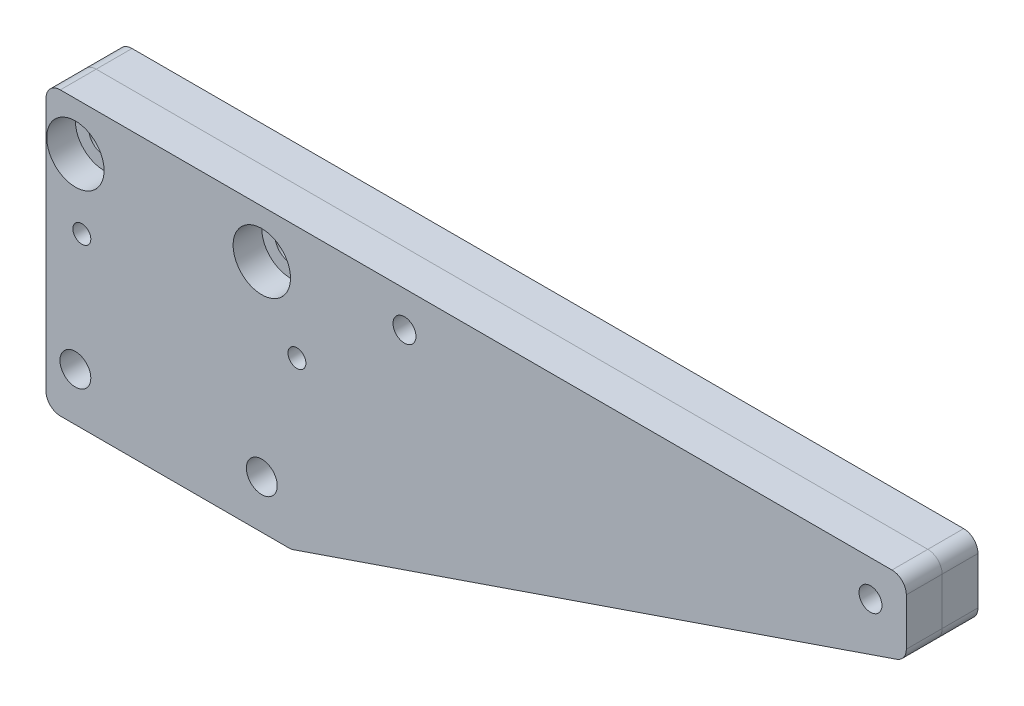
SolidWorks part; units mm, degrees
material "AISI 1045 Steel, cold drawn"
ref_plane "Front Plane" through (0, 0, 0) normal (0, 0, 1) x (1, 0, 0)
ref_plane "Top Plane" through (0, 0, 0) normal (0, 1, 0) x (1, 0, 0)
ref_plane "Right Plane" through (0, 0, 0) normal (1, 0, 0) x (0, 0, -1)
sketch "Sketch1" plane through (0, 0, 0) normal (0, 0, 1) x (1, 0, 0)
  line L0 (17.1, 19.7) -> (102.9, 19.7)
  line L1 (13, -13) -> (-13, -13) construction
  line L2 (13, -13) -> (13, 13) construction
  line L3 (13, 13) -> (-13, 13) construction
  line L4 (-13, -13) -> (-13, 13) construction
  line L5 (13, -13) -> (-13, 13) construction
  line L6 (13, 13) -> (-13, -13) construction
  line L7 (17.1, -19.7) -> (-17.1, -19.7)
  line L8 (17.1, -19.7) -> (17.1, 19.7) construction
  line L9 (17.1, 19.7) -> (-17.1, 19.7)
  line L10 (-17.1, -19.7) -> (-17.1, 19.7)
  line L11 (17.1, -19.7) -> (-17.1, 19.7) construction
  line L12 (17.1, 19.7) -> (-17.1, -19.7) construction
  line L13 (102.9, 19.7) -> (102.9, 9.7)
  line L14 (102.9, 9.7) -> (17.1, -19.7)
  point P0 (0, 0)
  point P6 (0, 0)
  dimension "D1" = 39.4
  dimension "D2" = 120
  dimension "D3" = 34.2
  dimension "D4" = 26
  dimension "D5" = 10
extrude "Boss-Extrude1" add sketch "Sketch1" along normal blind 5
hole_wizard "CBORE for M4 SHCS1" positions "Sketch2" profile "Sketch3" counterbore size "M4" standard "ANSI Metric" end condition through all
sketch "Sketch2" plane through (0, 0, 5) normal (0, 0, 1) x (1, 0, 0)
  point P0 (13, 13)
  point P3 (-13, 13)
sketch "Sketch3" plane through (13, 13, 5) normal (1, 0, 0) x (0, -1, 0)
  line L0 (0, 0) -> (0, 5)
  line L1 (0, 5) -> (2.15, 5)
  line L3 (2.15, 5) -> (2.15, 4)
  line L4 (2.15, 4) -> (4, 4)
  line L5 (4, 4) -> (4, 0)
  line L7 (4, 0) -> (0, 0)
  line L11 (0, -6.35) -> (0, 107.95) construction
  dimension "Thru Hole Dia." = 4.3
  dimension "Thru Hole Depth" = 5
  dimension "C'Bore Dia." = 8
  dimension "C'Bore Depth" = 4
hole_wizard "M4 Clearance Hole1" positions "Sketch10" profile "Sketch11" hole size "M4" standard "ANSI Metric" end condition through all
sketch "Sketch10" plane through (0, 0, 5) normal (0, 0, 1) x (1, 0, 0)
  point P0 (-13, -13)
  point P3 (13, -13)
sketch "Sketch11" plane through (-13, -13, 5) normal (1, 0, 0) x (0, -1, 0)
  line L0 (0, 0) -> (0, 5)
  line L1 (0, 5) -> (2.15, 5)
  line L2 (2.15, 5) -> (2.15, 0)
  line L5 (2.15, 0) -> (0, 0)
  line L11 (0, -6.35) -> (0, 107.95) construction
  dimension "Thru Hole Dia." = 4.3
  dimension "Thru Hole Depth" = 5
hole_wizard "Tap Drill for M3x0.5 Tap1" positions "Sketch4" profile "Sketch5" hole size "M3x0.5" standard "ANSI Metric" end condition through all
sketch "Sketch4" plane through (0, 0, 5) normal (0, 0, 1) x (1, 0, 0)
  line L0 (-12.1, 3.8) -> (17.9, 3.8) construction
  line L2 (102.9, 19.7) -> (-17.1, 19.7) construction
  line L3 (-17.1, 19.7) -> (-17.1, -19.7) construction
  point P0 (-12.1, 3.8)
  point P2 (17.9, 3.8)
  point P17 (2.9, 3.8)
  dimension "D1" = 15.9
  dimension "D2" = 30
  dimension "D3" = 20
sketch "Sketch5" plane through (-12.1, 3.8, 5) normal (1, 0, 0) x (0, -1, 0)
  line L0 (0, 0) -> (0, 5)
  line L1 (0, 5) -> (1.25, 5)
  line L2 (1.25, 5) -> (1.25, 0)
  line L5 (1.25, 0) -> (0, 0)
  line L11 (0, -6.35) -> (0, 107.95) construction
  dimension "Thru Hole Dia." = 2.5
  dimension "Thru Hole Depth" = 5
hole_wizard "M3 Clearance Hole2" positions "Sketch7" profile "Sketch9" hole size "M3" standard "ANSI Metric" end condition through all
sketch "Sketch7" plane through (0, 0, 0) normal (0, 0, -1) x (-1, 0, 0)
  line L1 (-97.9, 14.7) -> (-32.9, 14.7) construction
  line L3 (-102.9, 9.7) -> (-102.9, 19.7) construction
  line L4 (17.1, 19.7) -> (17.1, -19.7) construction
  point P0 (-97.9, 14.7)
  point P2 (-32.9, 14.7)
  point P21 (-102.9, 14.7)
  dimension "D1" = 115
  dimension "D2" = 65
sketch "Sketch9" plane through (97.9, 14.7, 0) normal (1, 0, 0) x (0, 1, 0)
  line L0 (0, 0) -> (0, 5)
  line L1 (0, 5) -> (1.6, 5)
  line L2 (1.6, 5) -> (1.6, 0)
  line L5 (1.6, 0) -> (0, 0)
  line L11 (0, -6.35) -> (0, 107.95) construction
  dimension "Thru Hole Dia." = 3.2
  dimension "Thru Hole Depth" = 5
fillet "Fillet1" radius 2 5 edges at (17.1, -19.7, 2.5) (-17.1, -19.7, 2.5) (102.9, 19.7, 2.5) (-17.1, 19.7, 2.5) (102.9, 9.7, 2.5)
mirror "Mirror1" about plane through (0, 0, 0) normal (0, 0, 1) of bodies 104
